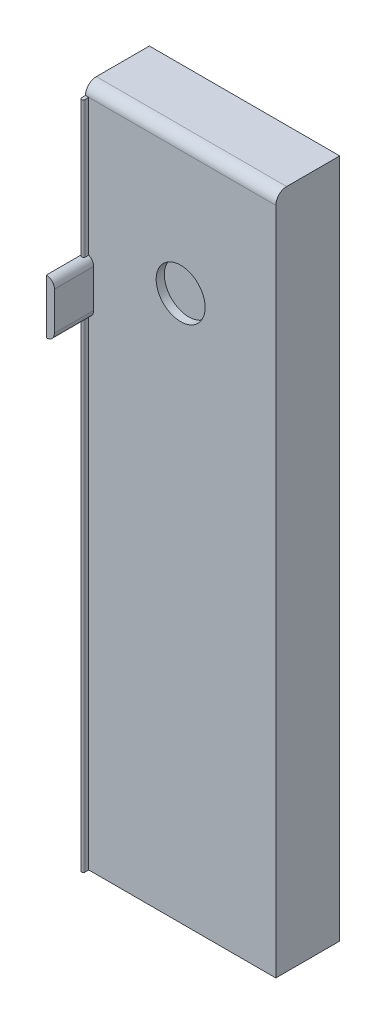
SolidWorks part; units mm, degrees
material "6061 Alloy"
ref_plane "Front Plane" through (0, 0, 0) normal (0, 0, 1) x (1, 0, 0)
ref_plane "Top Plane" through (0, 0, 0) normal (0, 1, 0) x (1, 0, 0)
ref_plane "Right Plane" through (0, 0, 0) normal (1, 0, 0) x (0, 0, -1)
sketch "Sketch1" plane through (0, 0, 0) normal (0, 0, 1) x (1, 0, 0)
  line L1 (-175, -625.25) -> (175, -625.25)
  line L2 (-175, -625.25) -> (-175, 625.25)
  line L3 (-175, 625.25) -> (175, 625.25)
  line L4 (175, -625.25) -> (175, 625.25)
  line L5 (0, 625.25) -> (0, -625.25) construction
  line L6 (-175, 0) -> (175, 0) construction
  point P0 (0, 0)
  dimension "D1" = 350
  dimension "D2" = 1250.5
extrude "Boss-Extrude1" add sketch "Sketch1" along normal blind 117.5
sketch "Sketch2" plane through (0, 0, 0) normal (0, 0, -1) x (-1, 0, 0)
  line L0 (175, -625.25) -> (-175, -625.25) construction
  circle A0 centre (0, -442) radius 15
  dimension "D1" = 30
  dimension "D2" = 183.25
extrude "Cut-Extrude1" cut sketch "Sketch2" against normal blind 5
sketch "Sketch3" plane through (0, 0, 117.5) normal (0, 0, 1) x (1, 0, 0)
  line L0 (175, 625.25) -> (-175, 625.25) construction
  line L1 (175, -625.25) -> (175, 625.25) construction
  circle A0 centre (0, 377.49) radius 45
  point P5 (0, 0)
  dimension "D2" = 90
  dimension "D1" = 247.76
  dimension "D3" = 175
extrude "Cut-Extrude2" cut sketch "Sketch3" against normal blind 15
fillet "Fillet3" radius 20 1 edges at (0, 625.25, 117.5) type face fillet first side face at (0, 625.25, 58.75) second side face at (45, 377.49, 117.5)
shell "Shell2" thickness 3
sketch "Sketch4" plane through (-175, 0, 0) normal (-1, 0, 0) x (0, 0, 1)
  line L5 (117.5, 605.25) -> (117.5, -625.25) construction
  line L6 (117.5, 605.25) -> (117.5, -625.25)
  line L7 (114.5863, 355.25) -> (189.5863, 355.25)
  line L8 (114.5863, 355.25) -> (114.5863, 255.25)
  line L9 (114.5863, 255.25) -> (189.5863, 255.25)
  line L10 (189.5863, 355.25) -> (189.5863, 255.25)
  line L11 (127.5, 605.25) -> (127.5, -625.25)
  line L12 (127.5, 605.25) -> (117.5, 605.25)
  line L13 (127.5, -625.25) -> (117.5, -625.25)
  point P11 (114.5863, 355.25)
  line M8 (117.5, -625.25) -> (117.5, 605.25)
  dimension "D1" = 75
  dimension "D2" = 100
  dimension "D4" = 250
  dimension "D3" = 10
extrude "Boss-Extrude2" add sketch "Sketch4" against normal blind 15 contours L7 L11 L9 L10 | L8 L7 L10 L9 region at (-175, 305.25, 158.5431)
extrude "Boss-Extrude3" add sketch "Sketch4<3>" against normal blind 6 contours L13 L11 L9 M8 | L11 L12 L6 L7 region at (-175, 480.25, 122.5) region at (-175, -185, 122.5)
sketch "Sketch4<3>" plane through (-175, 0, 0) normal (-1, 0, 0) x (0, 0, 1) same geometry as "Sketch4"
fillet "Fillet4" 2 edges at (-169, 480.25, 127.5) (-175, 480.25, 127.5) type full round first side face at (-169, 480.25, 122.5) second side face at (-175, 243.5642, 110.8315) middle face at (-172, 480.25, 127.5)
fillet "Fillet5" 2 edges at (-169, -185, 127.5) (-175, -185, 127.5) type full round first side face at (-169, -185, 122.5) second side face at (-175, 243.5642, 110.2315) middle face at (-172, -185, 127.5)
fillet "Fillet6" radius 15 1 edges at (-160, 355.25, 153.5431) type face fillet first side face at (-168, 355.25, 144.3621) second side face at (-160, 305.25, 153.5431)
fillet "Fillet7" radius 15 1 edges at (-160, 255.25, 153.5431) type face fillet first side face at (-160, 297.75, 153.5431) second side face at (-168, 255.25, 144.3621)
